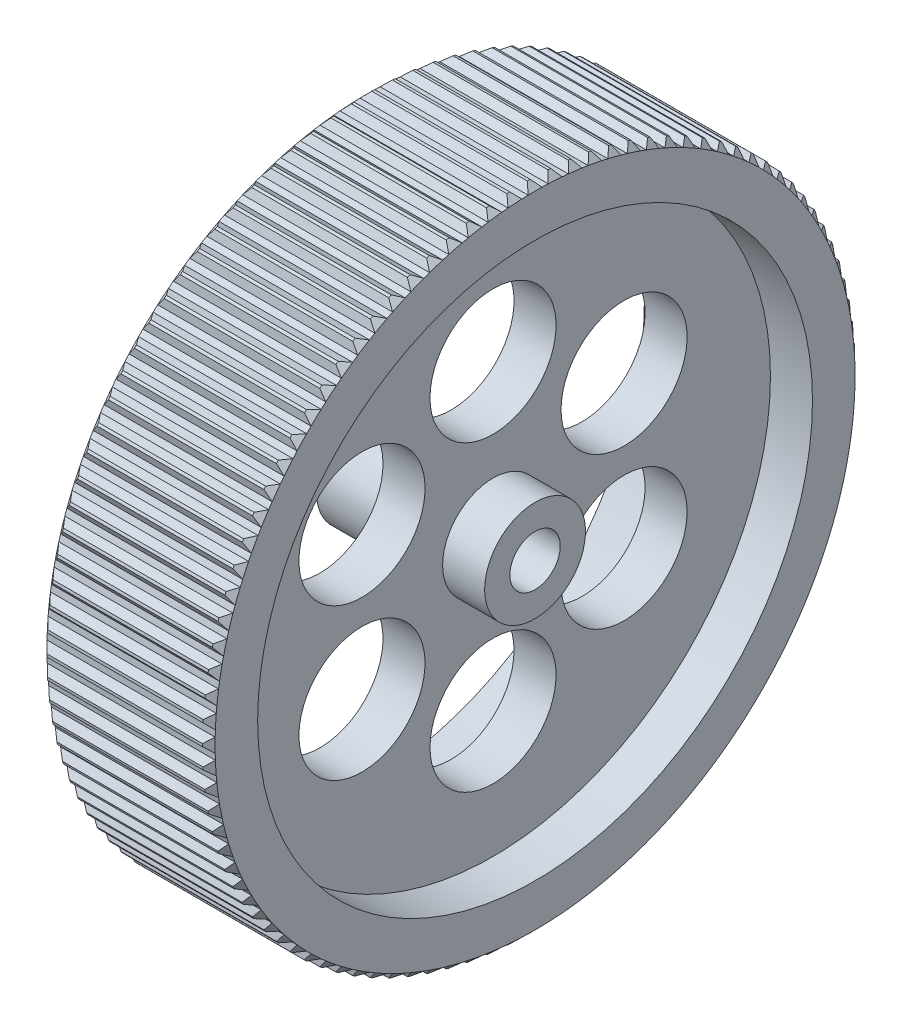
SolidWorks part; units mm, degrees
ref_plane "Front Plane" through (0, 0, 0) normal (0, 0, 1) x (1, 0, 0)
ref_plane "Top Plane" through (0, 0, 0) normal (0, 1, 0) x (1, 0, 0)
ref_plane "Right Plane" through (0, 0, 0) normal (1, 0, 0) x (0, 0, -1)
sketch "Sketch1" plane through (0, 0, 0) normal (0, 0, 1) x (1, 0, 0)
  line L0 (-38.06, 0) -> (7.5, 0) construction
  line L2 (-0.3486, 6) -> (-0.3486, 33)
  line L3 (-0.3486, 33) -> (-10.3486, 33)
  line L4 (-10.3486, 33) -> (-10.3486, 38)
  line L5 (-10.3486, 38) -> (9.6514, 38)
  line L7 (0, 3) -> (0, 19.4523) construction
  line L8 (9.6514, 38) -> (9.6514, 33)
  line L9 (9.6514, 33) -> (4.6514, 33)
  line L10 (4.6514, 33) -> (4.6514, 6)
  line L16 (7.5, 0) -> (40.3902, 0) construction
  line L17 (-10.3486, 3) -> (9.6514, 3)
  line L18 (-10.3486, 3) -> (-10.3486, 6)
  line L19 (-10.3486, 6) -> (-0.3486, 6)
  line L20 (9.6514, 6) -> (9.6514, 3)
  line L21 (4.6514, 6) -> (9.6514, 6)
  dimension "D1" = 20
  dimension "D2" = 5
  dimension "D3" = 10
  dimension "D4" = 3
  dimension "D5" = 5
  dimension "D6" = 3
  dimension "D7" = 0
  dimension "D8" = 38
revolve "Revolve1" add sketch "Sketch1" angle 360 about L0
sketch "Sketch2" plane through (-0.3486, 0, 0) normal (-1, 0, 0) x (0, 0, 1)
  line L0 (0, 0) -> (0, 18) construction
  circle A0 centre (0, 18) radius 7.5
  dimension "D2" = 15
  dimension "D1" = 18
extrude "Cut-Extrude1" cut sketch "Sketch2" against normal blind 10
pattern_circular "CirPattern2" count 6 over 360 about axis through (-38.06, 0, 0) along (-1, 0, 0) of "Cut-Extrude1" reverse direction yes
sketch "Sketch3" plane through (-10.3486, 0, 0) normal (-1, 0, 0) x (0, 0, 1)
  line L0 (0, 0) -> (0, 45.7966) construction
  line L1 (-0.8796, 37.9898) -> (0, 39)
  line L2 (0.8796, 37.9898) -> (0, 39)
  line L3 (-0.8796, 37.9898) -> (0, 35.9826)
  line L4 (0, 35.9826) -> (0.8796, 37.9898)
  line L5 (-3.2633, 37.8596) -> (-2.4488, 38.923)
  line L6 (-1.5075, 37.9701) -> (-2.4488, 38.923)
  line L7 (-3.2633, 37.8596) -> (-2.2594, 35.9116)
  line L8 (-2.2594, 35.9116) -> (-1.5075, 37.9701)
  line L9 (-5.6341, 37.58) -> (-4.888, 38.6925)
  line L10 (-3.8887, 37.8005) -> (-4.888, 38.6925)
  line L11 (-5.6341, 37.58) -> (-4.5098, 35.6989)
  line L12 (-4.5098, 35.6989) -> (-3.8887, 37.8005)
  line L13 (-7.9826, 37.1521) -> (-7.3079, 38.3092)
  line L14 (-6.2545, 37.4817) -> (-7.3079, 38.3092)
  line L15 (-7.9826, 37.1521) -> (-6.7425, 35.3453)
  line L16 (-6.7425, 35.3453) -> (-6.2545, 37.4817)
  line L17 (-10.2997, 36.5775) -> (-9.6989, 37.7747)
  line L18 (-8.5957, 37.0151) -> (-9.6989, 37.7747)
  line L19 (-10.2997, 36.5775) -> (-8.9485, 34.8522)
  line L20 (-8.9485, 34.8522) -> (-8.5957, 37.0151)
  line L21 (-12.5761, 35.8586) -> (-12.0517, 37.0912)
  line L22 (-10.9029, 36.4023) -> (-12.0517, 37.0912)
  line L23 (-12.5761, 35.8586) -> (-11.1192, 34.2215)
  line L24 (-11.1192, 34.2215) -> (-10.9029, 36.4023)
  line L25 (-14.8029, 34.9982) -> (-14.3569, 36.2613)
  line L26 (-13.1671, 35.6459) -> (-14.3569, 36.2613)
  line L27 (-14.8029, 34.9982) -> (-13.2461, 33.4558)
  line L28 (-13.2461, 33.4558) -> (-13.1671, 35.6459)
  line L29 (-16.9712, 33.9997) -> (-16.6054, 35.2883)
  line L30 (-15.3794, 34.7487) -> (-16.6054, 35.2883)
  line L31 (-16.9712, 33.9997) -> (-15.3207, 32.558)
  line L32 (-15.3207, 32.558) -> (-15.3794, 34.7487)
  line L33 (-19.0726, 32.867) -> (-18.7884, 34.176)
  line L34 (-17.5309, 33.7145) -> (-18.7884, 34.176)
  line L35 (-19.0726, 32.867) -> (-17.3348, 31.5318)
  line L36 (-17.3348, 31.5318) -> (-17.5309, 33.7145)
  line L37 (-21.0987, 31.6045) -> (-20.8972, 32.9288)
  line L38 (-19.6133, 32.5472) -> (-20.8972, 32.9288)
  line L39 (-21.0987, 31.6045) -> (-19.2805, 30.3811)
  line L40 (-19.2805, 30.3811) -> (-19.6133, 32.5472)
  line L41 (-23.0415, 30.2174) -> (-22.9236, 31.5517)
  line L42 (-21.6182, 31.2515) -> (-22.9236, 31.5517)
  line L43 (-23.0415, 30.2174) -> (-21.1501, 29.1105)
  line L44 (-21.1501, 29.1105) -> (-21.6182, 31.2515)
  line L45 (-24.8934, 28.711) -> (-24.8595, 30.05)
  line L46 (-23.5378, 29.8324) -> (-24.8595, 30.05)
  line L47 (-24.8934, 28.711) -> (-22.9362, 27.7251)
  line L48 (-22.9362, 27.7251) -> (-23.5378, 29.8324)
  line L49 (-26.6471, 27.0912) -> (-26.6973, 28.4298)
  line L50 (-25.3646, 28.2955) -> (-26.6973, 28.4298)
  line L51 (-26.6471, 27.0912) -> (-24.6318, 26.2302)
  line L52 (-24.6318, 26.2302) -> (-25.3646, 28.2955)
  line L53 (-28.2955, 25.3646) -> (-28.4298, 26.6973)
  line L54 (-27.0912, 26.6471) -> (-28.4298, 26.6973)
  line L55 (-28.2955, 25.3646) -> (-26.2302, 24.6318)
  line L56 (-26.2302, 24.6318) -> (-27.0912, 26.6471)
  line L57 (-29.8324, 23.5378) -> (-30.05, 24.8595)
  line L58 (-28.711, 24.8934) -> (-30.05, 24.8595)
  line L59 (-29.8324, 23.5378) -> (-27.7251, 22.9362)
  line L60 (-27.7251, 22.9362) -> (-28.711, 24.8934)
  line L61 (-31.2515, 21.6182) -> (-31.5517, 22.9236)
  line L62 (-30.2174, 23.0415) -> (-31.5517, 22.9236)
  line L63 (-31.2515, 21.6182) -> (-29.1105, 21.1501)
  line L64 (-29.1105, 21.1501) -> (-30.2174, 23.0415)
  line L65 (-32.5472, 19.6133) -> (-32.9288, 20.8972)
  line L66 (-31.6045, 21.0987) -> (-32.9288, 20.8972)
  line L67 (-32.5472, 19.6133) -> (-30.3811, 19.2805)
  line L68 (-30.3811, 19.2805) -> (-31.6045, 21.0987)
  line L69 (-33.7145, 17.5309) -> (-34.176, 18.7884)
  line L70 (-32.867, 19.0726) -> (-34.176, 18.7884)
  line L71 (-33.7145, 17.5309) -> (-31.5318, 17.3348)
  line L72 (-31.5318, 17.3348) -> (-32.867, 19.0726)
  line L73 (-34.7487, 15.3794) -> (-35.2883, 16.6054)
  line L74 (-33.9997, 16.9712) -> (-35.2883, 16.6054)
  line L75 (-34.7487, 15.3794) -> (-32.558, 15.3207)
  line L76 (-32.558, 15.3207) -> (-33.9997, 16.9712)
  line L77 (-35.6459, 13.1671) -> (-36.2613, 14.3569)
  line L78 (-34.9982, 14.8029) -> (-36.2613, 14.3569)
  line L79 (-35.6459, 13.1671) -> (-33.4558, 13.2461)
  line L80 (-33.4558, 13.2461) -> (-34.9982, 14.8029)
  line L81 (-36.4023, 10.9029) -> (-37.0912, 12.0517)
  line L82 (-35.8586, 12.5761) -> (-37.0912, 12.0517)
  line L83 (-36.4023, 10.9029) -> (-34.2215, 11.1192)
  line L84 (-34.2215, 11.1192) -> (-35.8586, 12.5761)
  line L85 (-37.0151, 8.5957) -> (-37.7747, 9.6989)
  line L86 (-36.5775, 10.2997) -> (-37.7747, 9.6989)
  line L87 (-37.0151, 8.5957) -> (-34.8522, 8.9485)
  line L88 (-34.8522, 8.9485) -> (-36.5775, 10.2997)
  line L89 (-37.4817, 6.2545) -> (-38.3092, 7.3079)
  line L90 (-37.1521, 7.9826) -> (-38.3092, 7.3079)
  line L91 (-37.4817, 6.2545) -> (-35.3453, 6.7425)
  line L92 (-35.3453, 6.7425) -> (-37.1521, 7.9826)
  line L93 (-37.8005, 3.8887) -> (-38.6925, 4.888)
  line L94 (-37.58, 5.6341) -> (-38.6925, 4.888)
  line L95 (-37.8005, 3.8887) -> (-35.6989, 4.5098)
  line L96 (-35.6989, 4.5098) -> (-37.58, 5.6341)
  line L97 (-37.9701, 1.5075) -> (-38.923, 2.4488)
  line L98 (-37.8596, 3.2633) -> (-38.923, 2.4488)
  line L99 (-37.9701, 1.5075) -> (-35.9116, 2.2594)
  line L100 (-35.9116, 2.2594) -> (-37.8596, 3.2633)
  line L101 (-37.9898, -0.8796) -> (-39, 0)
  line L102 (-37.9898, 0.8796) -> (-39, 0)
  line L103 (-37.9898, -0.8796) -> (-35.9826, 0)
  line L104 (-35.9826, 0) -> (-37.9898, 0.8796)
  line L105 (-37.8596, -3.2633) -> (-38.923, -2.4488)
  line L106 (-37.9701, -1.5075) -> (-38.923, -2.4488)
  line L107 (-37.8596, -3.2633) -> (-35.9116, -2.2594)
  line L108 (-35.9116, -2.2594) -> (-37.9701, -1.5075)
  line L109 (-37.58, -5.6341) -> (-38.6925, -4.888)
  line L110 (-37.8005, -3.8887) -> (-38.6925, -4.888)
  line L111 (-37.58, -5.6341) -> (-35.6989, -4.5098)
  line L112 (-35.6989, -4.5098) -> (-37.8005, -3.8887)
  line L113 (-37.1521, -7.9826) -> (-38.3092, -7.3079)
  line L114 (-37.4817, -6.2545) -> (-38.3092, -7.3079)
  line L115 (-37.1521, -7.9826) -> (-35.3453, -6.7425)
  line L116 (-35.3453, -6.7425) -> (-37.4817, -6.2545)
  line L117 (-36.5775, -10.2997) -> (-37.7747, -9.6989)
  line L118 (-37.0151, -8.5957) -> (-37.7747, -9.6989)
  line L119 (-36.5775, -10.2997) -> (-34.8522, -8.9485)
  line L120 (-34.8522, -8.9485) -> (-37.0151, -8.5957)
  line L121 (-35.8586, -12.5761) -> (-37.0912, -12.0517)
  line L122 (-36.4023, -10.9029) -> (-37.0912, -12.0517)
  line L123 (-35.8586, -12.5761) -> (-34.2215, -11.1192)
  line L124 (-34.2215, -11.1192) -> (-36.4023, -10.9029)
  line L125 (-34.9982, -14.8029) -> (-36.2613, -14.3569)
  line L126 (-35.6459, -13.1671) -> (-36.2613, -14.3569)
  line L127 (-34.9982, -14.8029) -> (-33.4558, -13.2461)
  line L128 (-33.4558, -13.2461) -> (-35.6459, -13.1671)
  line L129 (-33.9997, -16.9712) -> (-35.2883, -16.6054)
  line L130 (-34.7487, -15.3794) -> (-35.2883, -16.6054)
  line L131 (-33.9997, -16.9712) -> (-32.558, -15.3207)
  line L132 (-32.558, -15.3207) -> (-34.7487, -15.3794)
  line L133 (-32.867, -19.0726) -> (-34.176, -18.7884)
  line L134 (-33.7145, -17.5309) -> (-34.176, -18.7884)
  line L135 (-32.867, -19.0726) -> (-31.5318, -17.3348)
  line L136 (-31.5318, -17.3348) -> (-33.7145, -17.5309)
  line L137 (-31.6045, -21.0987) -> (-32.9288, -20.8972)
  line L138 (-32.5472, -19.6133) -> (-32.9288, -20.8972)
  line L139 (-31.6045, -21.0987) -> (-30.3811, -19.2805)
  line L140 (-30.3811, -19.2805) -> (-32.5472, -19.6133)
  line L141 (-30.2174, -23.0415) -> (-31.5517, -22.9236)
  line L142 (-31.2515, -21.6182) -> (-31.5517, -22.9236)
  line L143 (-30.2174, -23.0415) -> (-29.1105, -21.1501)
  line L144 (-29.1105, -21.1501) -> (-31.2515, -21.6182)
  line L145 (-28.711, -24.8934) -> (-30.05, -24.8595)
  line L146 (-29.8324, -23.5378) -> (-30.05, -24.8595)
  line L147 (-28.711, -24.8934) -> (-27.7251, -22.9362)
  line L148 (-27.7251, -22.9362) -> (-29.8324, -23.5378)
  line L149 (-27.0912, -26.6471) -> (-28.4298, -26.6973)
  line L150 (-28.2955, -25.3646) -> (-28.4298, -26.6973)
  line L151 (-27.0912, -26.6471) -> (-26.2302, -24.6318)
  line L152 (-26.2302, -24.6318) -> (-28.2955, -25.3646)
  line L153 (-25.3646, -28.2955) -> (-26.6973, -28.4298)
  line L154 (-26.6471, -27.0912) -> (-26.6973, -28.4298)
  line L155 (-25.3646, -28.2955) -> (-24.6318, -26.2302)
  line L156 (-24.6318, -26.2302) -> (-26.6471, -27.0912)
  line L157 (-23.5378, -29.8324) -> (-24.8595, -30.05)
  line L158 (-24.8934, -28.711) -> (-24.8595, -30.05)
  line L159 (-23.5378, -29.8324) -> (-22.9362, -27.7251)
  line L160 (-22.9362, -27.7251) -> (-24.8934, -28.711)
  line L161 (-21.6182, -31.2515) -> (-22.9236, -31.5517)
  line L162 (-23.0415, -30.2174) -> (-22.9236, -31.5517)
  line L163 (-21.6182, -31.2515) -> (-21.1501, -29.1105)
  line L164 (-21.1501, -29.1105) -> (-23.0415, -30.2174)
  line L165 (-19.6133, -32.5472) -> (-20.8972, -32.9288)
  line L166 (-21.0987, -31.6045) -> (-20.8972, -32.9288)
  line L167 (-19.6133, -32.5472) -> (-19.2805, -30.3811)
  line L168 (-19.2805, -30.3811) -> (-21.0987, -31.6045)
  line L169 (-17.5309, -33.7145) -> (-18.7884, -34.176)
  line L170 (-19.0726, -32.867) -> (-18.7884, -34.176)
  line L171 (-17.5309, -33.7145) -> (-17.3348, -31.5318)
  line L172 (-17.3348, -31.5318) -> (-19.0726, -32.867)
  line L173 (-15.3794, -34.7487) -> (-16.6054, -35.2883)
  line L174 (-16.9712, -33.9997) -> (-16.6054, -35.2883)
  line L175 (-15.3794, -34.7487) -> (-15.3207, -32.558)
  line L176 (-15.3207, -32.558) -> (-16.9712, -33.9997)
  line L177 (-13.1671, -35.6459) -> (-14.3569, -36.2613)
  line L178 (-14.8029, -34.9982) -> (-14.3569, -36.2613)
  line L179 (-13.1671, -35.6459) -> (-13.2461, -33.4558)
  line L180 (-13.2461, -33.4558) -> (-14.8029, -34.9982)
  line L181 (-10.9029, -36.4023) -> (-12.0517, -37.0912)
  line L182 (-12.5761, -35.8586) -> (-12.0517, -37.0912)
  line L183 (-10.9029, -36.4023) -> (-11.1192, -34.2215)
  line L184 (-11.1192, -34.2215) -> (-12.5761, -35.8586)
  line L185 (-8.5957, -37.0151) -> (-9.6989, -37.7747)
  line L186 (-10.2997, -36.5775) -> (-9.6989, -37.7747)
  line L187 (-8.5957, -37.0151) -> (-8.9485, -34.8522)
  line L188 (-8.9485, -34.8522) -> (-10.2997, -36.5775)
  line L189 (-6.2545, -37.4817) -> (-7.3079, -38.3092)
  line L190 (-7.9826, -37.1521) -> (-7.3079, -38.3092)
  line L191 (-6.2545, -37.4817) -> (-6.7425, -35.3453)
  line L192 (-6.7425, -35.3453) -> (-7.9826, -37.1521)
  line L193 (-3.8887, -37.8005) -> (-4.888, -38.6925)
  line L194 (-5.6341, -37.58) -> (-4.888, -38.6925)
  line L195 (-3.8887, -37.8005) -> (-4.5098, -35.6989)
  line L196 (-4.5098, -35.6989) -> (-5.6341, -37.58)
  line L197 (-1.5075, -37.9701) -> (-2.4488, -38.923)
  line L198 (-3.2633, -37.8596) -> (-2.4488, -38.923)
  line L199 (-1.5075, -37.9701) -> (-2.2594, -35.9116)
  line L200 (-2.2594, -35.9116) -> (-3.2633, -37.8596)
  line L201 (0.8796, -37.9898) -> (0, -39)
  line L202 (-0.8796, -37.9898) -> (0, -39)
  line L203 (0.8796, -37.9898) -> (0, -35.9826)
  line L204 (0, -35.9826) -> (-0.8796, -37.9898)
  line L205 (3.2633, -37.8596) -> (2.4488, -38.923)
  line L206 (1.5075, -37.9701) -> (2.4488, -38.923)
  line L207 (3.2633, -37.8596) -> (2.2594, -35.9116)
  line L208 (2.2594, -35.9116) -> (1.5075, -37.9701)
  line L209 (5.6341, -37.58) -> (4.888, -38.6925)
  line L210 (3.8887, -37.8005) -> (4.888, -38.6925)
  line L211 (5.6341, -37.58) -> (4.5098, -35.6989)
  line L212 (4.5098, -35.6989) -> (3.8887, -37.8005)
  line L213 (7.9826, -37.1521) -> (7.3079, -38.3092)
  line L214 (6.2545, -37.4817) -> (7.3079, -38.3092)
  line L215 (7.9826, -37.1521) -> (6.7425, -35.3453)
  line L216 (6.7425, -35.3453) -> (6.2545, -37.4817)
  line L217 (10.2997, -36.5775) -> (9.6989, -37.7747)
  line L218 (8.5957, -37.0151) -> (9.6989, -37.7747)
  line L219 (10.2997, -36.5775) -> (8.9485, -34.8522)
  line L220 (8.9485, -34.8522) -> (8.5957, -37.0151)
  line L221 (12.5761, -35.8586) -> (12.0517, -37.0912)
  line L222 (10.9029, -36.4023) -> (12.0517, -37.0912)
  line L223 (12.5761, -35.8586) -> (11.1192, -34.2215)
  line L224 (11.1192, -34.2215) -> (10.9029, -36.4023)
  line L225 (14.8029, -34.9982) -> (14.3569, -36.2613)
  line L226 (13.1671, -35.6459) -> (14.3569, -36.2613)
  line L227 (14.8029, -34.9982) -> (13.2461, -33.4558)
  line L228 (13.2461, -33.4558) -> (13.1671, -35.6459)
  line L229 (16.9712, -33.9997) -> (16.6054, -35.2883)
  line L230 (15.3794, -34.7487) -> (16.6054, -35.2883)
  line L231 (16.9712, -33.9997) -> (15.3207, -32.558)
  line L232 (15.3207, -32.558) -> (15.3794, -34.7487)
  line L233 (19.0726, -32.867) -> (18.7884, -34.176)
  line L234 (17.5309, -33.7145) -> (18.7884, -34.176)
  line L235 (19.0726, -32.867) -> (17.3348, -31.5318)
  line L236 (17.3348, -31.5318) -> (17.5309, -33.7145)
  line L237 (21.0987, -31.6045) -> (20.8972, -32.9288)
  line L238 (19.6133, -32.5472) -> (20.8972, -32.9288)
  line L239 (21.0987, -31.6045) -> (19.2805, -30.3811)
  line L240 (19.2805, -30.3811) -> (19.6133, -32.5472)
  line L241 (23.0415, -30.2174) -> (22.9236, -31.5517)
  line L242 (21.6182, -31.2515) -> (22.9236, -31.5517)
  line L243 (23.0415, -30.2174) -> (21.1501, -29.1105)
  line L244 (21.1501, -29.1105) -> (21.6182, -31.2515)
  line L245 (24.8934, -28.711) -> (24.8595, -30.05)
  line L246 (23.5378, -29.8324) -> (24.8595, -30.05)
  line L247 (24.8934, -28.711) -> (22.9362, -27.7251)
  line L248 (22.9362, -27.7251) -> (23.5378, -29.8324)
  line L249 (26.6471, -27.0912) -> (26.6973, -28.4298)
  line L250 (25.3646, -28.2955) -> (26.6973, -28.4298)
  line L251 (26.6471, -27.0912) -> (24.6318, -26.2302)
  line L252 (24.6318, -26.2302) -> (25.3646, -28.2955)
  line L253 (28.2955, -25.3646) -> (28.4298, -26.6973)
  line L254 (27.0912, -26.6471) -> (28.4298, -26.6973)
  line L255 (28.2955, -25.3646) -> (26.2302, -24.6318)
  line L256 (26.2302, -24.6318) -> (27.0912, -26.6471)
  line L257 (29.8324, -23.5378) -> (30.05, -24.8595)
  line L258 (28.711, -24.8934) -> (30.05, -24.8595)
  line L259 (29.8324, -23.5378) -> (27.7251, -22.9362)
  line L260 (27.7251, -22.9362) -> (28.711, -24.8934)
  line L261 (31.2515, -21.6182) -> (31.5517, -22.9236)
  line L262 (30.2174, -23.0415) -> (31.5517, -22.9236)
  line L263 (31.2515, -21.6182) -> (29.1105, -21.1501)
  line L264 (29.1105, -21.1501) -> (30.2174, -23.0415)
  line L265 (32.5472, -19.6133) -> (32.9288, -20.8972)
  line L266 (31.6045, -21.0987) -> (32.9288, -20.8972)
  line L267 (32.5472, -19.6133) -> (30.3811, -19.2805)
  line L268 (30.3811, -19.2805) -> (31.6045, -21.0987)
  line L269 (33.7145, -17.5309) -> (34.176, -18.7884)
  line L270 (32.867, -19.0726) -> (34.176, -18.7884)
  line L271 (33.7145, -17.5309) -> (31.5318, -17.3348)
  line L272 (31.5318, -17.3348) -> (32.867, -19.0726)
  line L273 (34.7487, -15.3794) -> (35.2883, -16.6054)
  line L274 (33.9997, -16.9712) -> (35.2883, -16.6054)
  line L275 (34.7487, -15.3794) -> (32.558, -15.3207)
  line L276 (32.558, -15.3207) -> (33.9997, -16.9712)
  line L277 (35.6459, -13.1671) -> (36.2613, -14.3569)
  line L278 (34.9982, -14.8029) -> (36.2613, -14.3569)
  line L279 (35.6459, -13.1671) -> (33.4558, -13.2461)
  line L280 (33.4558, -13.2461) -> (34.9982, -14.8029)
  line L281 (36.4023, -10.9029) -> (37.0912, -12.0517)
  line L282 (35.8586, -12.5761) -> (37.0912, -12.0517)
  line L283 (36.4023, -10.9029) -> (34.2215, -11.1192)
  line L284 (34.2215, -11.1192) -> (35.8586, -12.5761)
  line L285 (37.0151, -8.5957) -> (37.7747, -9.6989)
  line L286 (36.5775, -10.2997) -> (37.7747, -9.6989)
  line L287 (37.0151, -8.5957) -> (34.8522, -8.9485)
  line L288 (34.8522, -8.9485) -> (36.5775, -10.2997)
  line L289 (37.4817, -6.2545) -> (38.3092, -7.3079)
  line L290 (37.1521, -7.9826) -> (38.3092, -7.3079)
  line L291 (37.4817, -6.2545) -> (35.3453, -6.7425)
  line L292 (35.3453, -6.7425) -> (37.1521, -7.9826)
  line L293 (37.8005, -3.8887) -> (38.6925, -4.888)
  line L294 (37.58, -5.6341) -> (38.6925, -4.888)
  line L295 (37.8005, -3.8887) -> (35.6989, -4.5098)
  line L296 (35.6989, -4.5098) -> (37.58, -5.6341)
  line L297 (37.9701, -1.5075) -> (38.923, -2.4488)
  line L298 (37.8596, -3.2633) -> (38.923, -2.4488)
  line L299 (37.9701, -1.5075) -> (35.9116, -2.2594)
  line L300 (35.9116, -2.2594) -> (37.8596, -3.2633)
  line L301 (37.9898, 0.8796) -> (39, 0)
  line L302 (37.9898, -0.8796) -> (39, 0)
  line L303 (37.9898, 0.8796) -> (35.9826, 0)
  line L304 (35.9826, 0) -> (37.9898, -0.8796)
  line L305 (37.8596, 3.2633) -> (38.923, 2.4488)
  line L306 (37.9701, 1.5075) -> (38.923, 2.4488)
  line L307 (37.8596, 3.2633) -> (35.9116, 2.2594)
  line L308 (35.9116, 2.2594) -> (37.9701, 1.5075)
  line L309 (37.58, 5.6341) -> (38.6925, 4.888)
  line L310 (37.8005, 3.8887) -> (38.6925, 4.888)
  line L311 (37.58, 5.6341) -> (35.6989, 4.5098)
  line L312 (35.6989, 4.5098) -> (37.8005, 3.8887)
  line L313 (37.1521, 7.9826) -> (38.3092, 7.3079)
  line L314 (37.4817, 6.2545) -> (38.3092, 7.3079)
  line L315 (37.1521, 7.9826) -> (35.3453, 6.7425)
  line L316 (35.3453, 6.7425) -> (37.4817, 6.2545)
  line L317 (36.5775, 10.2997) -> (37.7747, 9.6989)
  line L318 (37.0151, 8.5957) -> (37.7747, 9.6989)
  line L319 (36.5775, 10.2997) -> (34.8522, 8.9485)
  line L320 (34.8522, 8.9485) -> (37.0151, 8.5957)
  line L321 (35.8586, 12.5761) -> (37.0912, 12.0517)
  line L322 (36.4023, 10.9029) -> (37.0912, 12.0517)
  line L323 (35.8586, 12.5761) -> (34.2215, 11.1192)
  line L324 (34.2215, 11.1192) -> (36.4023, 10.9029)
  line L325 (34.9982, 14.8029) -> (36.2613, 14.3569)
  line L326 (35.6459, 13.1671) -> (36.2613, 14.3569)
  line L327 (34.9982, 14.8029) -> (33.4558, 13.2461)
  line L328 (33.4558, 13.2461) -> (35.6459, 13.1671)
  line L329 (33.9997, 16.9712) -> (35.2883, 16.6054)
  line L330 (34.7487, 15.3794) -> (35.2883, 16.6054)
  line L331 (33.9997, 16.9712) -> (32.558, 15.3207)
  line L332 (32.558, 15.3207) -> (34.7487, 15.3794)
  line L333 (32.867, 19.0726) -> (34.176, 18.7884)
  line L334 (33.7145, 17.5309) -> (34.176, 18.7884)
  line L335 (32.867, 19.0726) -> (31.5318, 17.3348)
  line L336 (31.5318, 17.3348) -> (33.7145, 17.5309)
  line L337 (31.6045, 21.0987) -> (32.9288, 20.8972)
  line L338 (32.5472, 19.6133) -> (32.9288, 20.8972)
  line L339 (31.6045, 21.0987) -> (30.3811, 19.2805)
  line L340 (30.3811, 19.2805) -> (32.5472, 19.6133)
  line L341 (30.2174, 23.0415) -> (31.5517, 22.9236)
  line L342 (31.2515, 21.6182) -> (31.5517, 22.9236)
  line L343 (30.2174, 23.0415) -> (29.1105, 21.1501)
  line L344 (29.1105, 21.1501) -> (31.2515, 21.6182)
  line L345 (28.711, 24.8934) -> (30.05, 24.8595)
  line L346 (29.8324, 23.5378) -> (30.05, 24.8595)
  line L347 (28.711, 24.8934) -> (27.7251, 22.9362)
  line L348 (27.7251, 22.9362) -> (29.8324, 23.5378)
  line L349 (27.0912, 26.6471) -> (28.4298, 26.6973)
  line L350 (28.2955, 25.3646) -> (28.4298, 26.6973)
  line L351 (27.0912, 26.6471) -> (26.2302, 24.6318)
  line L352 (26.2302, 24.6318) -> (28.2955, 25.3646)
  line L353 (25.3646, 28.2955) -> (26.6973, 28.4298)
  line L354 (26.6471, 27.0912) -> (26.6973, 28.4298)
  line L355 (25.3646, 28.2955) -> (24.6318, 26.2302)
  line L356 (24.6318, 26.2302) -> (26.6471, 27.0912)
  line L357 (23.5378, 29.8324) -> (24.8595, 30.05)
  line L358 (24.8934, 28.711) -> (24.8595, 30.05)
  line L359 (23.5378, 29.8324) -> (22.9362, 27.7251)
  line L360 (22.9362, 27.7251) -> (24.8934, 28.711)
  line L361 (21.6182, 31.2515) -> (22.9236, 31.5517)
  line L362 (23.0415, 30.2174) -> (22.9236, 31.5517)
  line L363 (21.6182, 31.2515) -> (21.1501, 29.1105)
  line L364 (21.1501, 29.1105) -> (23.0415, 30.2174)
  line L365 (19.6133, 32.5472) -> (20.8972, 32.9288)
  line L366 (21.0987, 31.6045) -> (20.8972, 32.9288)
  line L367 (19.6133, 32.5472) -> (19.2805, 30.3811)
  line L368 (19.2805, 30.3811) -> (21.0987, 31.6045)
  line L369 (17.5309, 33.7145) -> (18.7884, 34.176)
  line L370 (19.0726, 32.867) -> (18.7884, 34.176)
  line L371 (17.5309, 33.7145) -> (17.3348, 31.5318)
  line L372 (17.3348, 31.5318) -> (19.0726, 32.867)
  line L373 (15.3794, 34.7487) -> (16.6054, 35.2883)
  line L374 (16.9712, 33.9997) -> (16.6054, 35.2883)
  line L375 (15.3794, 34.7487) -> (15.3207, 32.558)
  line L376 (15.3207, 32.558) -> (16.9712, 33.9997)
  line L377 (13.1671, 35.6459) -> (14.3569, 36.2613)
  line L378 (14.8029, 34.9982) -> (14.3569, 36.2613)
  line L379 (13.1671, 35.6459) -> (13.2461, 33.4558)
  line L380 (13.2461, 33.4558) -> (14.8029, 34.9982)
  line L381 (10.9029, 36.4023) -> (12.0517, 37.0912)
  line L382 (12.5761, 35.8586) -> (12.0517, 37.0912)
  line L383 (10.9029, 36.4023) -> (11.1192, 34.2215)
  line L384 (11.1192, 34.2215) -> (12.5761, 35.8586)
  line L385 (8.5957, 37.0151) -> (9.6989, 37.7747)
  line L386 (10.2997, 36.5775) -> (9.6989, 37.7747)
  line L387 (8.5957, 37.0151) -> (8.9485, 34.8522)
  line L388 (8.9485, 34.8522) -> (10.2997, 36.5775)
  line L389 (6.2545, 37.4817) -> (7.3079, 38.3092)
  line L390 (7.9826, 37.1521) -> (7.3079, 38.3092)
  line L391 (6.2545, 37.4817) -> (6.7425, 35.3453)
  line L392 (6.7425, 35.3453) -> (7.9826, 37.1521)
  line L393 (3.8887, 37.8005) -> (4.888, 38.6925)
  line L394 (5.6341, 37.58) -> (4.888, 38.6925)
  line L395 (3.8887, 37.8005) -> (4.5098, 35.6989)
  line L396 (4.5098, 35.6989) -> (5.6341, 37.58)
  line L397 (1.5075, 37.9701) -> (2.4488, 38.923)
  line L398 (3.2633, 37.8596) -> (2.4488, 38.923)
  line L399 (1.5075, 37.9701) -> (2.2594, 35.9116)
  line L400 (2.2594, 35.9116) -> (3.2633, 37.8596)
  circle A0 centre (0, 0) radius 38 construction
  circle A1 centre (0, 0) radius 38 construction
  point P409 (0, 0)
  dimension "D1" = 39
  dimension "D2" = 1.7593
  dimension "D3" = 100
extrude "Boss-Extrude1" add sketch "Sketch3" against normal up to surface (20 mm away) up to face at (9.6514, 0, 38)
sketch "Sketch4" plane through (0, 0, 0) normal (0, 1, 0) x (1, 0, 0)
  point P0 (0, 0)
sketch "Sketch5" plane through (9.6514, 0, 0) normal (1, 0, 0) x (0, 0, -1)
  circle A0 centre (0, 0) radius 38.8103
  circle A1 centre (0, 0) radius 76.3264
extrude "Cut-Extrude2" cut sketch "Sketch5" against normal through all both and the other way through all
sketch "Sketch7" plane through (0, 0, 0) normal (0, 1, 0) x (1, 0, 0)
  line L0 (9.6514, -0.1655) -> (9.6514, 0.1655) construction
  line L1 (-9.5986, 38.8099) -> (8.9014, 38.8099)
  line L2 (-10.3486, 38.0599) -> (-10.3486, 0)
  line L4 (9.6514, 38.0599) -> (9.6514, 0)
  line L5 (-10.3486, 38.8099) -> (9.6514, 0) construction
  line L6 (-10.3486, 0) -> (9.6514, 38.8099) construction
  line L7 (-10.3486, 38.0599) -> (-9.5986, 38.8099)
  line L8 (8.9014, 38.8099) -> (9.6514, 38.0599)
  line L9 (-10.3486, 0) -> (-20.7379, 0)
  line L10 (-20.7379, 0) -> (-20.7379, 56.7836)
  line L11 (-20.7379, 56.7836) -> (26.3195, 56.7836)
  line L12 (26.3195, 56.7836) -> (26.3195, 0)
  line L13 (26.3195, 0) -> (9.6514, 0)
  line L14 (-10.3486, 0) -> (9.6514, 0) construction
  point P4 (-0.3486, 19.405)
revolve "Cut-Revolve1" cut sketch "Sketch7" angle 360 about L14
sketch "Sketch8" plane through (-10.3486, 0, 0) normal (-1, 0, 0) x (0, 0, 1)
  circle A0 centre (0, 0) radius 38.0599
  circle A1 centre (0, 0) radius 38.0599
  arc A2 (16.9491, 34.0776) -> (15.4535, 34.7814) centre (0, 0) ccw construction
  circle A3 centre (0, 0) radius 35.7571
extrude "Boss-Extrude2" add sketch "Sketch8" against normal up to surface (20 mm away) contours A0 A3 region at (-10.3486, 0, -36.9834)
